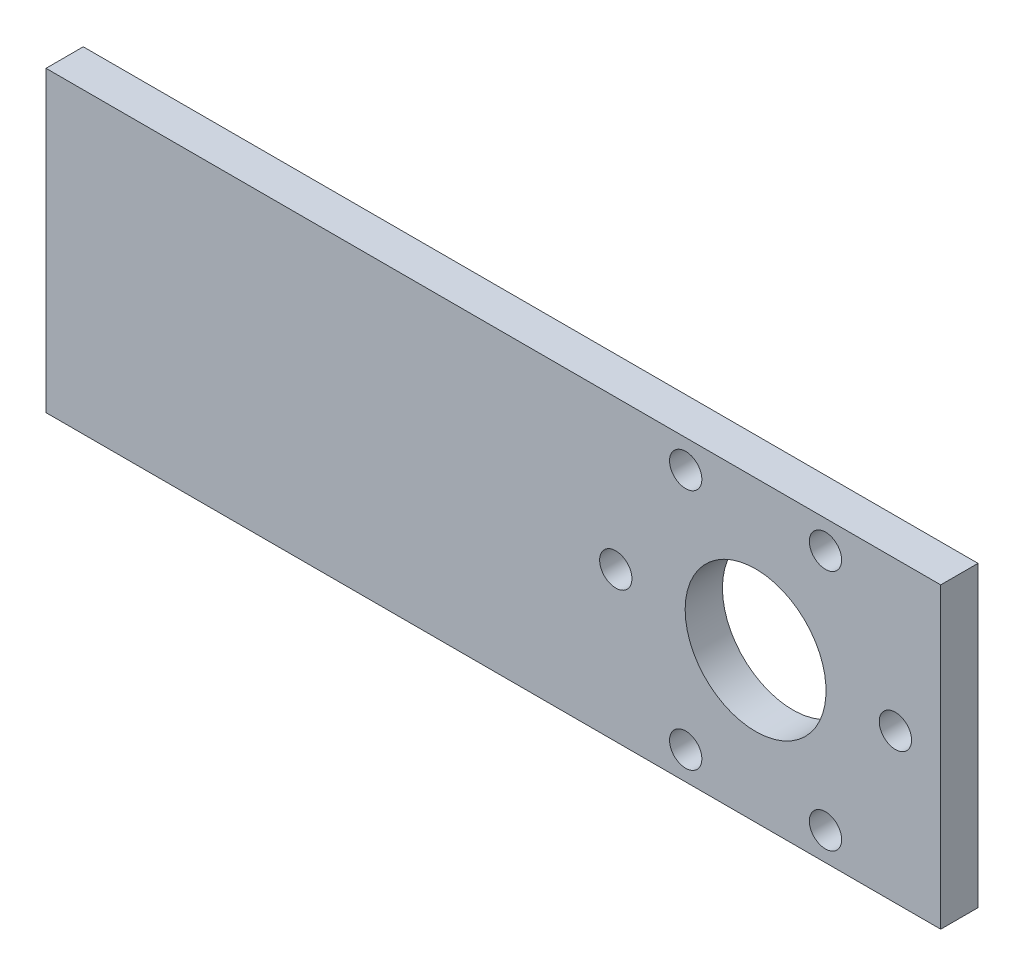
SolidWorks part; units mm, degrees
ref_plane "Front Plane" through (0, 0, 0) normal (0, 0, 1) x (1, 0, 0)
ref_plane "Top Plane" through (0, 0, 0) normal (0, 1, 0) x (1, 0, 0)
ref_plane "Right Plane" through (0, 0, 0) normal (1, 0, 0) x (0, 0, -1)
sketch "Sketch1" plane through (0, 0, 0) normal (0, 0, 1) x (1, 0, 0)
  line L1 (0, 0) -> (152.4, 0)
  line L2 (0, 0) -> (0, -50.8)
  line L3 (0, -50.8) -> (152.4, -50.8)
  line L4 (152.4, 0) -> (152.4, -50.8)
  dimension "D1" = 50.8
  dimension "D2" = 152.4
extrude "Boss-Extrude1" add sketch "Sketch1" along normal blind 6.35
sketch "Sketch2" plane through (0, 0, 0) normal (0, 0, -1) x (-1, 0, 0)
  line L0 (-152.4, -50.8) -> (-152.4, 0) construction
  circle A0 centre (-120.866, -25.4) radius 12
  point P5 (-152.4, -25.4)
  dimension "D1" = 24
extrude "Cut-Extrude1" cut sketch "Sketch2" against normal through all
sketch "Sketch3" plane through (0, 0, 0) normal (0, 0, -1) x (-1, 0, 0)
  circle A1 centre (-108.9597, -4.7778) radius 2.5527 construction
  circle A3 centre (-132.7722, -4.7778) radius 2.5527 construction
  circle A5 centre (-144.6785, -25.4) radius 2.5527 construction
  circle A7 centre (-97.0535, -25.4) radius 2.5527 construction
  circle A9 centre (-132.7722, -46.0222) radius 2.5527 construction
  circle A11 centre (-108.9597, -46.0222) radius 2.5527 construction
  circle A12 centre (-108.9597, -4.7778) radius 2.75
  circle A13 centre (-132.7722, -4.7778) radius 2.75
  circle A14 centre (-144.6785, -25.4) radius 2.75
  circle A15 centre (-132.7722, -46.0222) radius 2.75
  circle A16 centre (-108.9597, -46.0222) radius 2.75
  circle A17 centre (-97.0535, -25.4) radius 2.75
  dimension "D1" = 5.5
  dimension "D2" = 5.5
  dimension "D3" = 5.5
  dimension "D4" = 5.5
  dimension "D5" = 5.5
  dimension "D6" = 5.5
extrude "Cut-Extrude2" cut sketch "Sketch3" against normal through all
